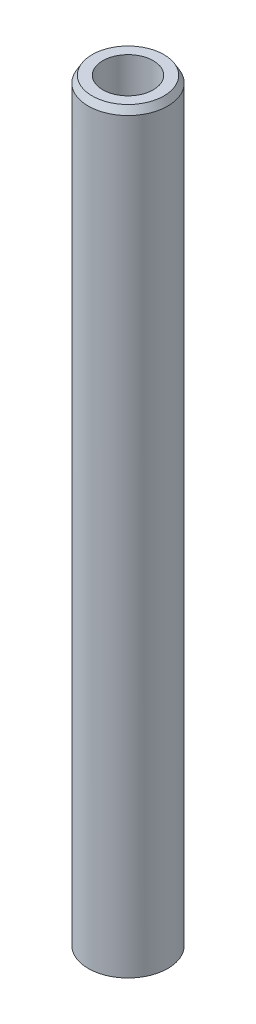
SolidWorks part; units mm, degrees
ref_plane "Front Plane" through (0, 0, 0) normal (0, 0, 1) x (1, 0, 0)
ref_plane "Top Plane" through (0, 0, 0) normal (0, 1, 0) x (1, 0, 0)
ref_plane "Right Plane" through (0, 0, 0) normal (1, 0, 0) x (0, 0, -1)
sketch "Sketch1" plane through (0, 0, 0) normal (0, 1, 0) x (1, 0, 0)
  circle A0 centre (0, 0) radius 22.5
  dimension "SHAFT_OD" = 45
extrude "Boss-Extrude1" add sketch "Sketch1" along normal blind 428.5574
sketch "Sketch2" plane through (0, 0, 0) normal (0, 1, 0) x (1, 0, 0)
  circle A0 centre (0, 0) radius 14.2929
  dimension "BORE_D" = 28.5858
extrude "Cut-Extrude1" cut sketch "Sketch2" along normal through all
chamfer "Chamfer1" distance 3.8436 angle 30 2 edges at (0, 428.5574, 22.5) (0, 0, 22.5) first distance on face at (0, 428.5574, 22.5) first distance on face at (0, 0, 14.2929)
